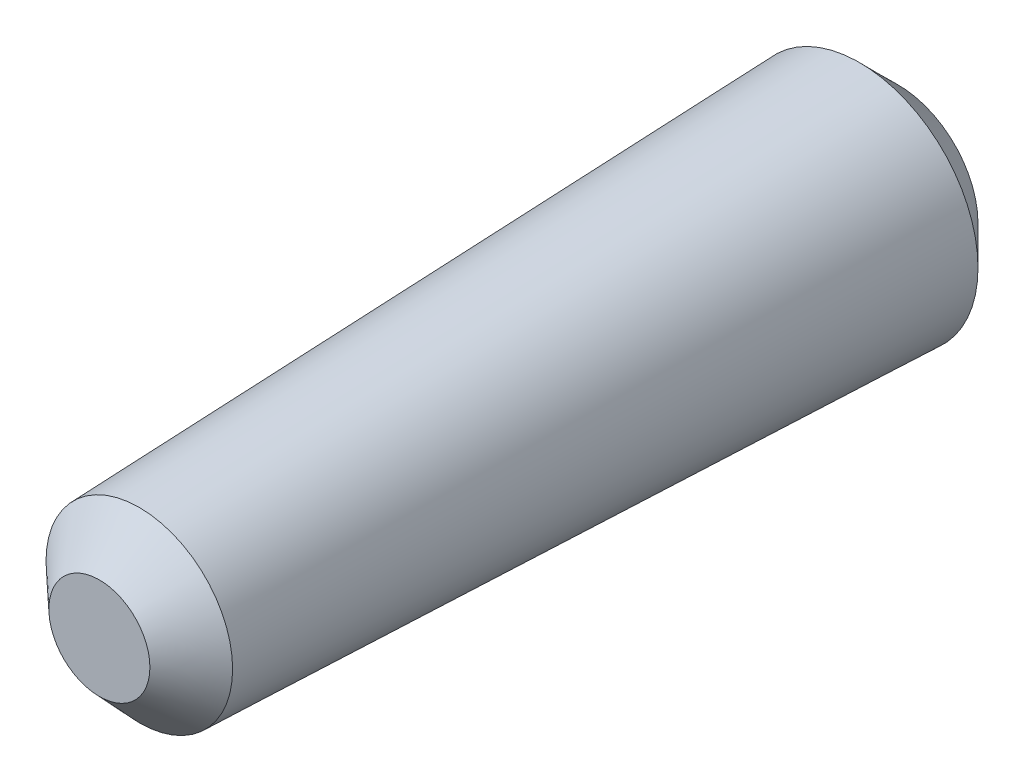
SolidWorks part; units mm, degrees
ref_plane "前视基准面" through (0, 0, 0) normal (0, 0, 1) x (1, 0, 0)
ref_plane "上视基准面" through (0, 0, 0) normal (0, 1, 0) x (1, 0, 0)
ref_plane "右视基准面" through (0, 0, 0) normal (1, 0, 0) x (0, 0, -1)
other "Configuration Table"
sketch "草图1" plane through (0, 0, 0) normal (0, 0, 1) x (1, 0, 0)
  circle A0 centre (0, 0) radius 3
  dimension "D1" = 6
extrude "凸台-拉伸1" add sketch "草图1" along normal blind 20 draft 2
chamfer "倒角1" distance 1 angle 45 2 edges at (3, 0, 0) (2.3016, 0, 20) first distance on face at (3, 0, 0) first distance on face at (2.3016, 0, 20)
